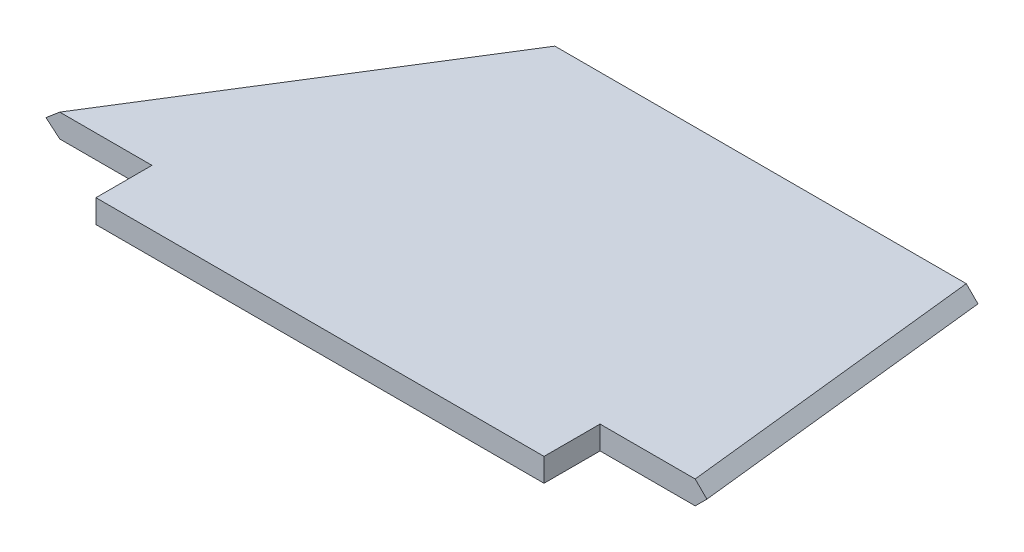
SolidWorks part; units mm, degrees
ref_plane "Front Plane" through (0, 0, 0) normal (0, 0, 1) x (1, 0, 0)
ref_plane "Top Plane" through (0, 0, 0) normal (0, 1, 0) x (1, 0, 0)
ref_plane "Right Plane" through (0, 0, 0) normal (1, 0, 0) x (0, 0, -1)
sketch "Sketch1" plane through (0, 0, 0) normal (0, 1, 0) x (1, 0, 0)
  line L0 (0, 0) -> (152.4, 0)
  line L1 (152.4, 0) -> (144.78, 69.088)
  line L2 (144.78, 69.088) -> (43.18, 69.088)
  line L3 (43.18, 69.088) -> (0, 0)
  dimension "D1" = 152.4
  dimension "D2" = 101.6
  dimension "D3" = 43.18
  dimension "D4" = 69.088
extrude "Boss-Extrude1" add sketch "Sketch1" along normal blind 5.2832
sketch "Sketch2" plane through (0, 0, 0) normal (0, 1, 0) x (1, 0, 0)
  line L0 (25.4, 0) -> (25.4, -12.7)
  line L1 (0, 0) -> (152.4, 0) construction
  line L2 (25.4, -12.7) -> (127, -12.7)
  line L3 (127, -12.7) -> (127, 0)
  line L8 (43.18, 69.088) -> (0, 0)
  line L9 (0, 0) -> (152.4, 0)
  line L10 (152.4, 0) -> (144.78, 69.088)
  line L11 (144.78, 69.088) -> (43.18, 69.088)
  line L13 (25.4, 0) -> (127, 0)
  dimension "D1" = 101.6
  dimension "D2" = 12.7
  dimension "D3" = 12.7
  dimension "D4" = 25.4
  dimension "D5" = 25.4
  dimension "D6" = 0
extrude "Boss-Extrude2" add sketch "Sketch2" along normal blind 5.2832
chamfer "Chamfer1" distance 3.81 angle 45 2 edges at (21.59, 5.2832, -34.544) (21.59, 0, -34.544)
chamfer "Chamfer2" distance 3.81 angle 45 2 edges at (148.59, 0, -34.544) (148.59, 5.2832, -34.544)
